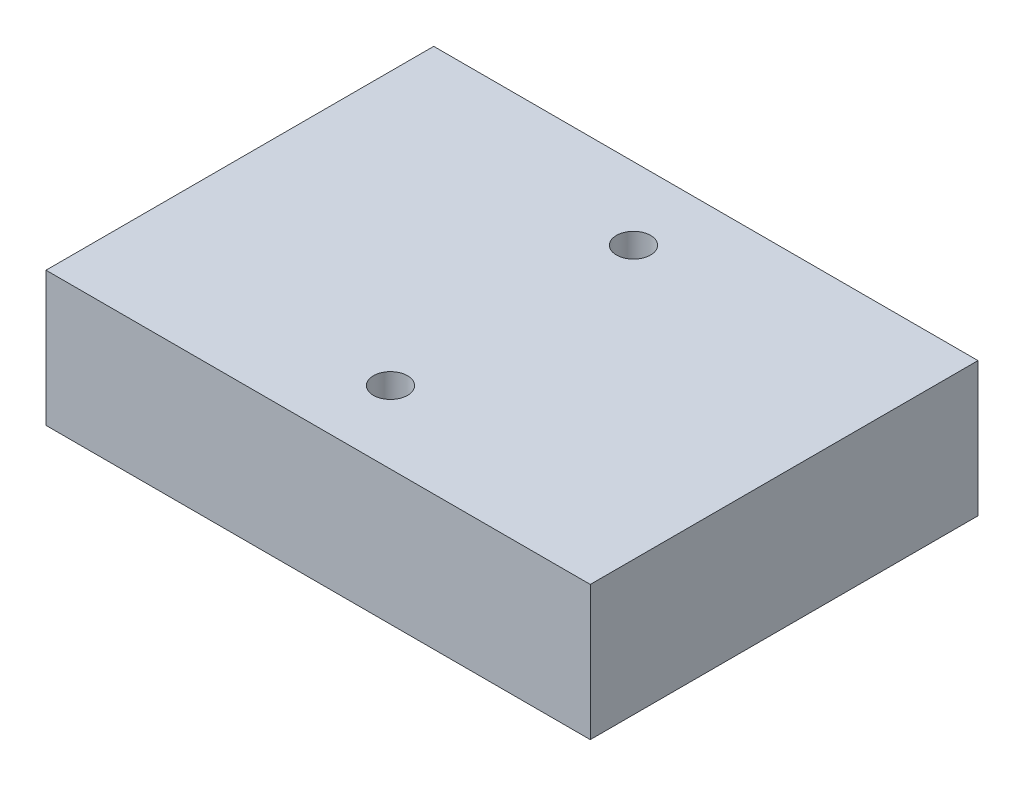
SolidWorks part; units mm, degrees
ref_plane "Front Plane" through (0, 0, 0) normal (0, 0, 1) x (1, 0, 0)
ref_plane "Top Plane" through (0, 0, 0) normal (0, 1, 0) x (1, 0, 0)
ref_plane "Right Plane" through (0, 0, 0) normal (1, 0, 0) x (0, 0, -1)
sketch "Sketch1" plane through (0, 0, 0) normal (0, 1, 0) x (1, 0, 0)
  line L1 (26.315, -18.745) -> (-26.315, -18.745)
  line L2 (26.315, -18.745) -> (26.315, 18.745)
  line L3 (26.315, 18.745) -> (-26.315, 18.745)
  line L4 (-26.315, -18.745) -> (-26.315, 18.745)
  line L5 (26.315, -18.745) -> (-26.315, 18.745) construction
  line L6 (26.315, 18.745) -> (-26.315, -18.745) construction
  point P0 (0, 0)
  dimension "D1" = 52.63
  dimension "D2" = 37.49
extrude "Boss-Extrude1" add sketch "Sketch1" along normal blind 13
sketch "Sketch2" plane through (0, 13, 0) normal (0, 1, 0) x (1, 0, 0)
  line L0 (-26.315, -18.745) -> (26.315, -18.745) construction
  circle A0 centre (0, 11.75) radius 1.65
  circle A1 centre (0, -11.75) radius 1.65
  dimension "D1" = 23.5
  dimension "D2" = 6.995
extrude "Cut-Extrude1" cut sketch "Sketch2" against normal through all
